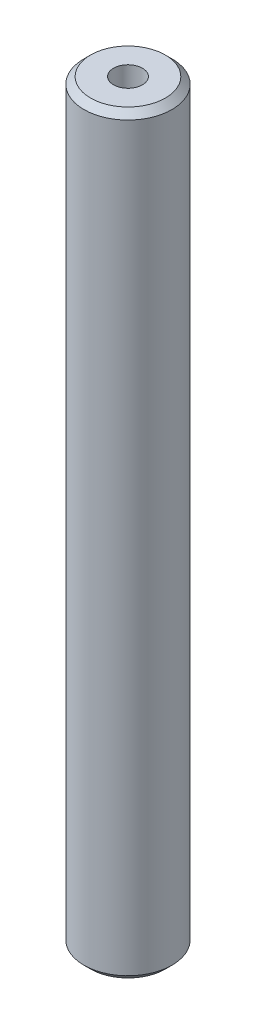
SolidWorks part; units mm, degrees
ref_plane "Front Plane" through (0, 0, 0) normal (0, 0, 1) x (1, 0, 0)
ref_plane "Top Plane" through (0, 0, 0) normal (0, 1, 0) x (1, 0, 0)
ref_plane "Right Plane" through (0, 0, 0) normal (1, 0, 0) x (0, 0, -1)
sketch "Sketch1" plane through (0, 0, 0) normal (0, 1, 0) x (1, 0, 0)
  circle A0 centre (0, 0) radius 35
  dimension "SHAFT_OD" = 70
extrude "Boss-Extrude1" add sketch "Sketch1" along normal blind 600
sketch "Sketch2" plane through (0, 0, 0) normal (0, 1, 0) x (1, 0, 0)
  circle A0 centre (0, 0) radius 11.4889
  dimension "BORE_D" = 22.9779
extrude "Cut-Extrude1" cut sketch "Sketch2" along normal through all
chamfer "Chamfer1" distance 5.2724 angle 45 2 edges at (0, 600, 35) (0, 0, 35)
